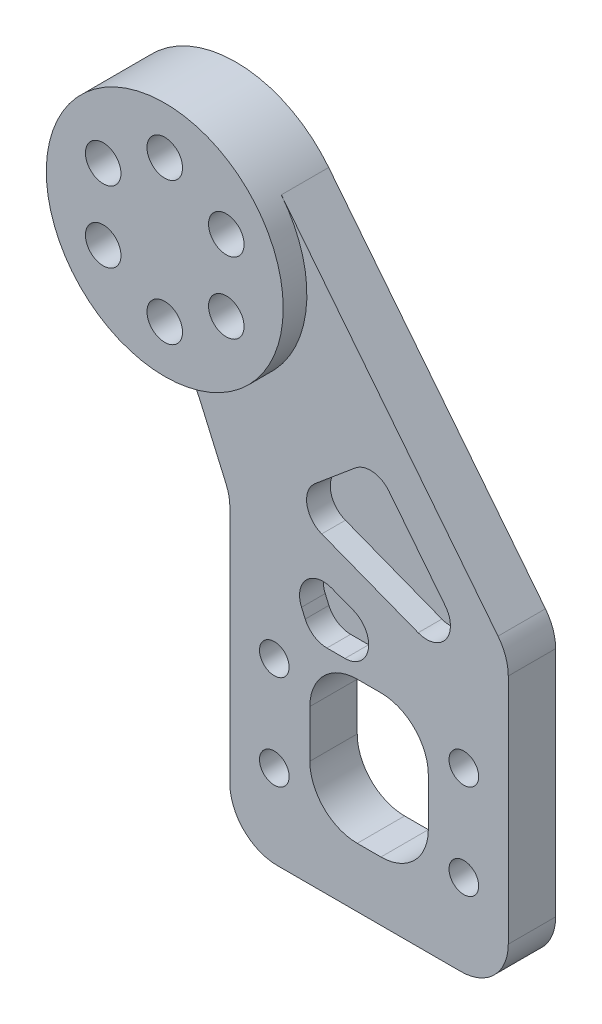
SolidWorks part; units mm, degrees
material "6061-T4 (SS)"
ref_plane "前视基准面" through (0, 0, 0) normal (0, 0, 1) x (1, 0, 0)
ref_plane "上视基准面" through (0, 0, 0) normal (0, 1, 0) x (1, 0, 0)
ref_plane "右视基准面" through (0, 0, 0) normal (1, 0, 0) x (0, 0, -1)
other "Configuration Table"
sketch "草图1" plane through (0, 0, 0) normal (0, 0, 1) x (1, 0, 0)
  line L0 (0, -5.5) -> (0, 0) construction
  line L1 (-11.75, -16.5) -> (11.75, -16.5)
  line L2 (-11.75, -16.5) -> (-11.75, 16.5)
  line L3 (-11.75, 16.5) -> (11.75, 16.5)
  line L4 (11.75, -16.5) -> (11.75, 16.5)
  line L5 (-11.75, -16.5) -> (11.75, 16.5) construction
  line L6 (-11.75, 16.5) -> (11.75, -16.5) construction
  line L7 (-8, -9.5) -> (8, -9.5) construction
  line L8 (-8, -9.5) -> (-8, -1.5) construction
  line L9 (-8, -1.5) -> (8, -1.5) construction
  line L10 (8, -9.5) -> (8, -1.5) construction
  line L11 (-8, -9.5) -> (8, -1.5) construction
  line L12 (-8, -1.5) -> (8, -9.5) construction
  line L13 (-11.75, 16.5) -> (-15.25, 16.5)
  line L14 (11.75, 16.5) -> (-8.7361, 34.0875)
  circle A0 centre (8, -1.5) radius 1.25
  circle A1 centre (8, -9.5) radius 1.25
  circle A2 centre (-8, -9.5) radius 1.25
  circle A3 centre (-8, -1.5) radius 1.25
  circle A4 centre (-15.25, 26.5) radius 10
  point P0 (0, 0)
  point P6 (0, -5.5)
  dimension "D3" = 2.5
  dimension "D7" = 32
  dimension "D8" = 27
  dimension "D9" = 20
  dimension "D1" = 33
  dimension "D2" = 23.5
  dimension "D4" = 16
  dimension "D5" = 8
extrude "凸台-拉伸1" add sketch "草图1" along normal blind 4 contours A4 | A4 L13 L3 L14 | L1 L4 L3 L2 A3 A2 A1 A0
sketch "草图2" plane through (0, 0, 4) normal (0, 0, 1) x (1, 0, 0)
  circle A0 centre (-15.25, 26.5) radius 10
  arc A1 (-8.7361, 34.0875) -> (-15.25, 16.5) centre (-15.25, 26.5) ccw construction
extrude "凸台-拉伸2" add sketch "草图2" along normal blind 2
sketch "草图3" plane through (0, 0, 6) normal (0, 0, 1) x (1, 0, 0)
  circle A0 centre (-15.25, 26.5) radius 6 construction
  circle A1 centre (-15.25, 32.5) radius 1.5
  circle A2 centre (-10.0538, 29.5) radius 1.5
  circle A3 centre (-10.0538, 23.5) radius 1.5
  circle A4 centre (-15.25, 20.5) radius 1.5
  circle A5 centre (-20.4462, 23.5) radius 1.5
  circle A6 centre (-20.4462, 29.5) radius 1.5
  point P17 (-15.25, 26.5)
  dimension "D1" = 12
  dimension "D2" = 3
  dimension "D3" = 6
extrude "切除-拉伸1" cut sketch "草图3" against normal blind 6
sketch "草图4" plane through (0, 0, 4) normal (0, 0, 1) x (1, 0, 0)
  line L0 (-8, -1.5) -> (8, -9.5) construction
  line L1 (-11.75, -16.5) -> (11.75, -16.5) construction
  line L2 (-5, -11.5) -> (5, -11.5)
  line L3 (-5, -11.5) -> (-5, 0.5)
  line L4 (-5, 0.5) -> (5, 0.5)
  line L5 (5, -11.5) -> (5, 0.5)
  line L6 (-5, -11.5) -> (5, 0.5) construction
  line L7 (-5, 0.5) -> (5, -11.5) construction
  circle A0 centre (-8, -1.5) radius 1.25 construction
  point P3 (0, -5.5)
  dimension "D1" = 5
  dimension "D2" = 3
extrude "切除-拉伸2" cut sketch "草图4" against normal blind 6
sketch "草图5" [suppressed] plane through (0, 0, 6) normal (0, 0, 1) x (1, 0, 0)
  circle A1 centre (-15.25, 26.5) radius 10
  circle A2 centre (-15.25, 26.5) radius 10
  dimension "D1" = 0
extrude "切除-拉伸3" [suppressed] cut sketch "草图5" against normal blind 2
sketch "草图6" plane through (0, 0, 0) normal (0, 0, -1) x (-1, 0, 0)
  circle A0 centre (15.25, 26.5) radius 10
  arc A1 (15.25, 16.5) -> (8.7361, 34.0875) centre (15.25, 26.5) ccw construction
  circle A2 centre (10.0538, 23.5) radius 1.5 construction
  circle A3 centre (15.25, 20.5) radius 1.5 construction
  circle A4 centre (20.4462, 23.5) radius 1.5 construction
  circle A5 centre (15.25, 32.5) radius 1.5 construction
  circle A6 centre (20.4462, 29.5) radius 1.5 construction
  circle A7 centre (10.0538, 29.5) radius 1.5 construction
  circle A8 centre (10.0538, 23.5) radius 1.5
  circle A9 centre (15.25, 20.5) radius 1.5
  circle A10 centre (20.4462, 23.5) radius 1.5
  circle A11 centre (15.25, 32.5) radius 1.5
  circle A12 centre (20.4462, 29.5) radius 1.5
  circle A13 centre (10.0538, 29.5) radius 1.5
extrude "凸台-拉伸3" [suppressed] add sketch "草图6" along normal blind 2
sketch "草图7" plane through (0, 0, 4) normal (0, 0, 1) x (1, 0, 0)
  line L0 (11.75, 8.5) -> (-7.4089, 32.7062)
  line L1 (11.75, -16.5) -> (11.75, 16.5) construction
  line L2 (-11.75, -16.5) -> (11.75, -16.5) construction
  line L8 (11.75, -16.5) -> (11.75, 16.5)
  line L9 (11.75, 16.5) -> (-8.7361, 34.0875)
  line L10 (-15.25, 16.5) -> (-11.75, 16.5)
  line L11 (-11.75, 16.5) -> (-11.75, -16.5)
  line L12 (-11.75, -16.5) -> (11.75, -16.5)
  line L13 (11.75, -16.5) -> (11.75, 16.5)
  line L14 (11.75, 16.5) -> (-8.7361, 34.0875)
  line L15 (-15.25, 16.5) -> (-11.75, 16.5)
  line L16 (-11.75, 16.5) -> (-11.75, -16.5)
  line L17 (-11.75, -16.5) -> (11.75, -16.5)
  circle A1 centre (-15.25, 26.5) radius 10
  arc A8 (-15.25, 16.5) -> (-8.7361, 34.0875) centre (-15.25, 26.5) ccw
  arc A13 (-15.25, 16.5) -> (-8.7361, 34.0875) centre (-15.25, 26.5) ccw
  dimension "D1" = 25
  dimension "D2" = 0
extrude "切除-拉伸4" cut sketch "草图7" against normal blind 10
sketch "草图8" plane through (0, 0, 4) normal (0, 0, 1) x (1, 0, 0)
  line L0 (-15.25, 16.5) -> (-11.75, 8.5)
  line L1 (-11.75, -16.5) -> (-11.75, 16.5) construction
  line L2 (-11.75, 8.5) -> (-11.75, 16.5)
  line L3 (-11.75, 16.5) -> (-15.25, 16.5)
  line L4 (-11.75, -16.5) -> (11.75, -16.5) construction
  dimension "D1" = 25
extrude "凸台-拉伸4" add sketch "草图8" against normal blind 4
fillet "圆角1" radius 4 5 edges at (-11.75, -16.5, 2) (11.75, -16.5, 2) (11.75, 8.5, 2) (-15.25, 16.5, 2) (-11.75, 8.5, 2)
sketch "草图9" plane through (0, 0, 4) normal (0, 0, 1) x (1, 0, 0)
  line L0 (-4.8672, 1.5) -> (12.8268, 1.5)
  line L1 (12.8268, 1.5) -> (0.4144, 17.1823)
  line L2 (-4.8672, 1.5) -> (-8.4746, 9.7454)
  line L3 (-8.4746, 9.7454) -> (0.4144, 17.1823)
  line L4 (-14.3194, 14.3728) -> (-12.0854, 9.2666) construction
  line L5 (10.8865, 9.591) -> (-7.4089, 32.7062) construction
  line L6 (-8.4746, 9.7454) -> (12.8268, 1.5) construction
  line L7 (-7.1602, 10.8451) -> (10.9914, 3.8189)
  line L8 (8.6715, 1.5) -> (-7.6274, 7.809)
  circle A0 centre (-8, -1.5) radius 1.25 construction
  dimension "D1" = 3
  dimension "D2" = 3.5
  dimension "D3" = 3.5
  dimension "D4" = 9
  dimension "D5" = 20
  dimension "D6" = 1.5
  dimension "D7" = 1.5
extrude "切除-拉伸5" cut sketch "草图9" against normal blind 2 contours L0 L8 L2 | L3 L7 L1
fillet "圆角2" radius 2 6 edges at (0.4144, 17.1823, 3) (-7.1602, 10.8451, 3) (-7.6274, 7.809, 3) (8.6715, 1.5, 3) (-4.8672, 1.5, 3) (10.9914, 3.8189, 3)
fillet "圆角3" radius 4 4 edges at (-5, -11.5, 2) (5, 0.5, 2) (5, -11.5, 2) (-5, 0.5, 2)
